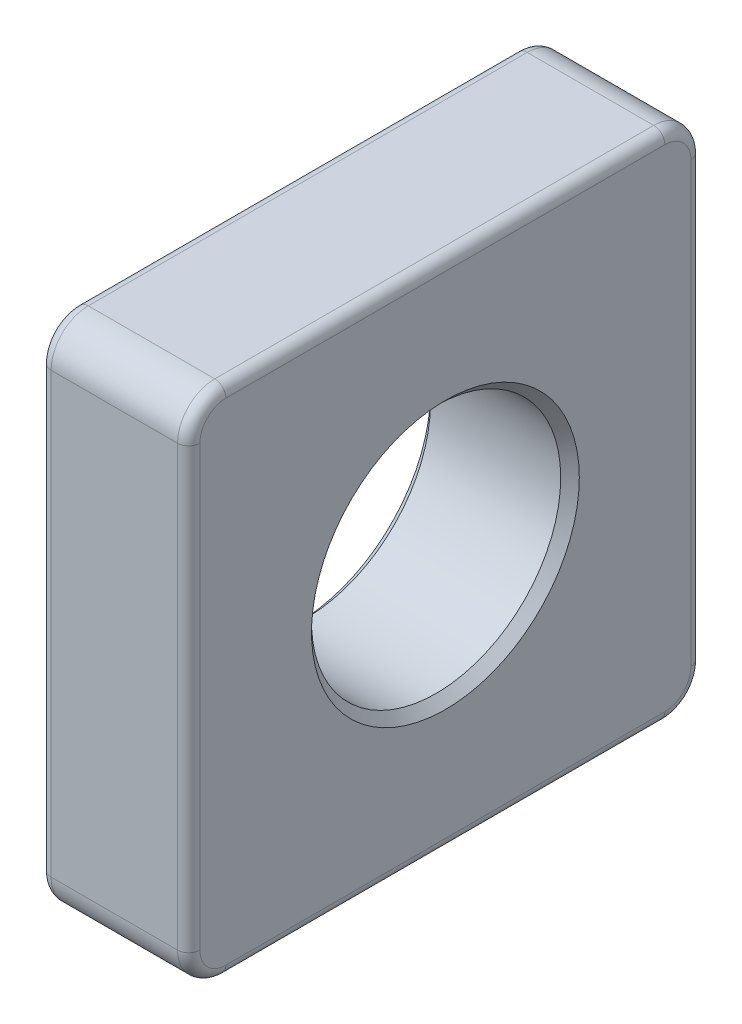
SolidWorks part; units mm, degrees
ref_plane "Front" through (0, 0, 0) normal (0, 0, 1) x (1, 0, 0)
ref_plane "Top" through (0, 0, 0) normal (0, 1, 0) x (1, 0, 0)
ref_plane "Right" through (0, 0, 0) normal (1, 0, 0) x (0, 0, -1)
sketch "Sketch1" plane through (0, 0, 0) normal (1, 0, 0) x (0, 0, -1)
  line L1 (6.9, -6.9) -> (-6.9, -6.9)
  line L2 (6.9, -6.9) -> (6.9, 6.9)
  line L3 (6.9, 6.9) -> (-6.9, 6.9)
  line L4 (-6.9, -6.9) -> (-6.9, 6.9)
  line L5 (6.9, -6.9) -> (-6.9, 6.9) construction
  line L6 (6.9, 6.9) -> (-6.9, -6.9) construction
  point P0 (0, 0)
  dimension "D1" = 6.9
  dimension "D2" = 13.8
extrude "Boss-Extrude1" add sketch "Sketch1" along normal blind 4
sketch "Sketch2" plane through (0, 0, 0) normal (1, 0, 0) x (0, 0, -1)
  circle A0 centre (0, 0) radius 3.35
  dimension "D1" = 6.7
extrude "Cut-Extrude1" cut sketch "Sketch2" along normal through all
chamfer "Chamfer1" distance 0.25 angle 45 2 edges at (0, 0, -3.35) (4, 0, -3.35)
fillet "Fillet1" radius 1 4 edges at (2, 6.9, -6.9) (2, -6.9, -6.9) (2, -6.9, 6.9) (2, 6.9, 6.9)
fillet "Fillet2" radius 0.3 16 edges at (0, 6.6071, 6.6071) (0, 6.9, 0) (0, 6.6071, -6.6071) (0, 0, -6.9) (0, -6.6071, -6.6071) (0, -6.9, 0) (0, -6.6071, 6.6071) (4, -6.6071, 6.6071) (4, 0, 6.9) (4, 6.6071, 6.6071) (4, 6.9, 0) (4, 6.6071, -6.6071) (4, 0, -6.9) (4, -6.6071, -6.6071) (0, 0, 6.9) (4, -6.9, 0)
equation "\"D2@Sketch1\"=2*\"D1@Sketch1\""
